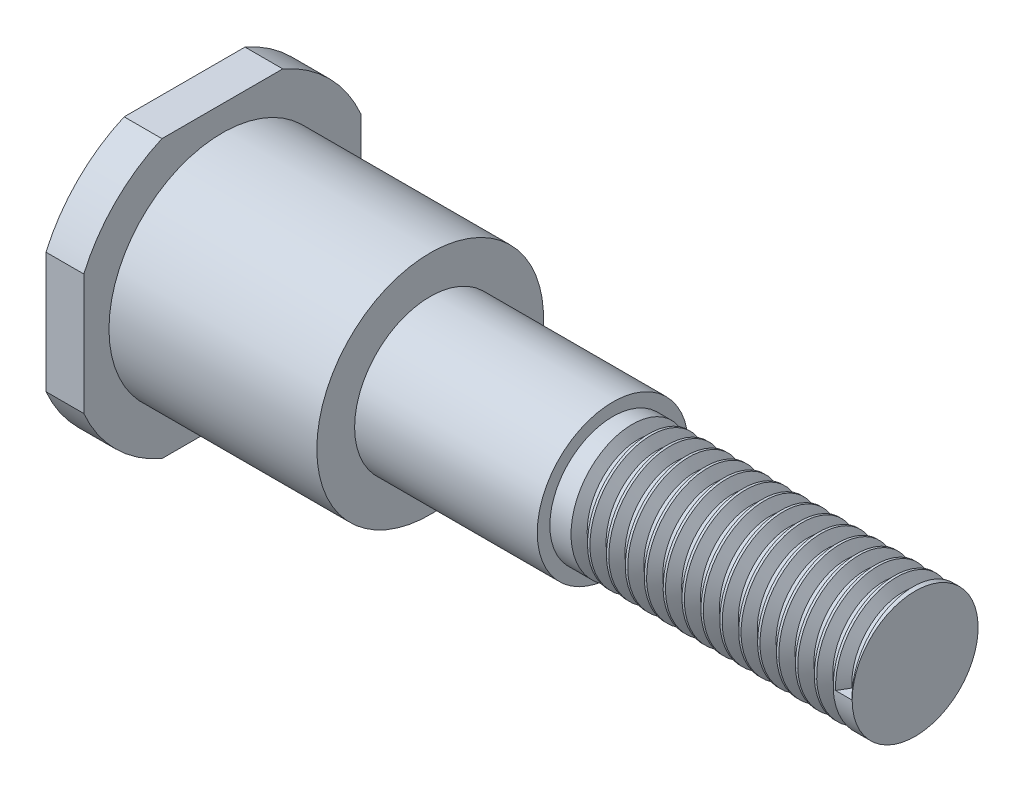
SolidWorks part; units mm, degrees
material "A3钢"
ref_plane "前视基准面" through (0, 0, 0) normal (0, 0, 1) x (1, 0, 0)
ref_plane "上视基准面" through (0, 0, 0) normal (0, 1, 0) x (1, 0, 0)
ref_plane "右视基准面" through (0, 0, 0) normal (1, 0, 0) x (0, 0, -1)
sketch "草图1" plane through (0, 0, 0) normal (0, 0, 1) x (1, 0, 0)
  line L0 (0, 0) -> (0, 12)
  line L1 (0, 12) -> (3, 12)
  line L2 (3, 12) -> (3, 9)
  line L3 (3, 9) -> (19.5, 9)
  line L4 (19.5, 9) -> (19.5, 6)
  line L5 (19.5, 6) -> (34, 6)
  line L6 (34, 6) -> (34, 5)
  line L7 (58, 0) -> (0, 0)
  line L8 (-3.6102, 0) -> (118.9367, 0) construction
  line L9 (34, 5) -> (58, 5)
  line L10 (58, 5) -> (58, 0)
  dimension "D1" = 24
  dimension "D2" = 18
  dimension "D3" = 12
  dimension "D4" = 10
  dimension "D5" = 16.5
  dimension "D6" = 3
  dimension "D7" = 58
  dimension "D8" = 14.5
revolve "旋转1" add sketch "草图1" angle 360 about L8
sketch "草图5" plane through (0, 0, 0) normal (-1, 0, 0) x (0, 0, 1)
  line L1 (-11, -11) -> (11, -11)
  line L2 (-11, -11) -> (-11, 11)
  line L3 (-11, 11) -> (11, 11)
  line L4 (11, -11) -> (11, 11)
  line L5 (-11, -11) -> (11, 11) construction
  line L6 (-11, 11) -> (11, -11) construction
  point P0 (0, 0)
  dimension "D1" = 22
  dimension "D2" = 22
extrude "切除-拉伸1" cut sketch "草图5" against normal through all flip side to cut
thread "螺纹线1" pitch 1.5 method cut profile "螺纹线轮廓1" start angle 0, offset 0, length 22, pitch 1.5, diameter 10
ref_plane "基准面1" through (58, 0, 5) normal (0, -1, 0) x (0, 0, 1)
sketch "螺纹线轮廓1" plane through (58, 0, 5) normal (0, -1, 0) x (0, 0, 1)
  line L0 (0, 0) -> (0, 1.5) construction
  line L11 (0, 0) -> (0, 1.3125)
  line L12 (0, 1.3125) -> (-0.8119, 0.8437)
  line L13 (-0.8119, 0.8437) -> (-0.8119, 0.4687)
  line L15 (-0.8119, 0.4687) -> (0, 0)
  line L17 (-0.8119, 0.6562) -> (0, 0.6562) construction
  point P2 (0, 0)
  dimension "Pitch" = 1.5
  dimension "Profile_Angle" = 60
  dimension "Profile_Land" = 0.375
  dimension "Profile_Height" = 0.8119
